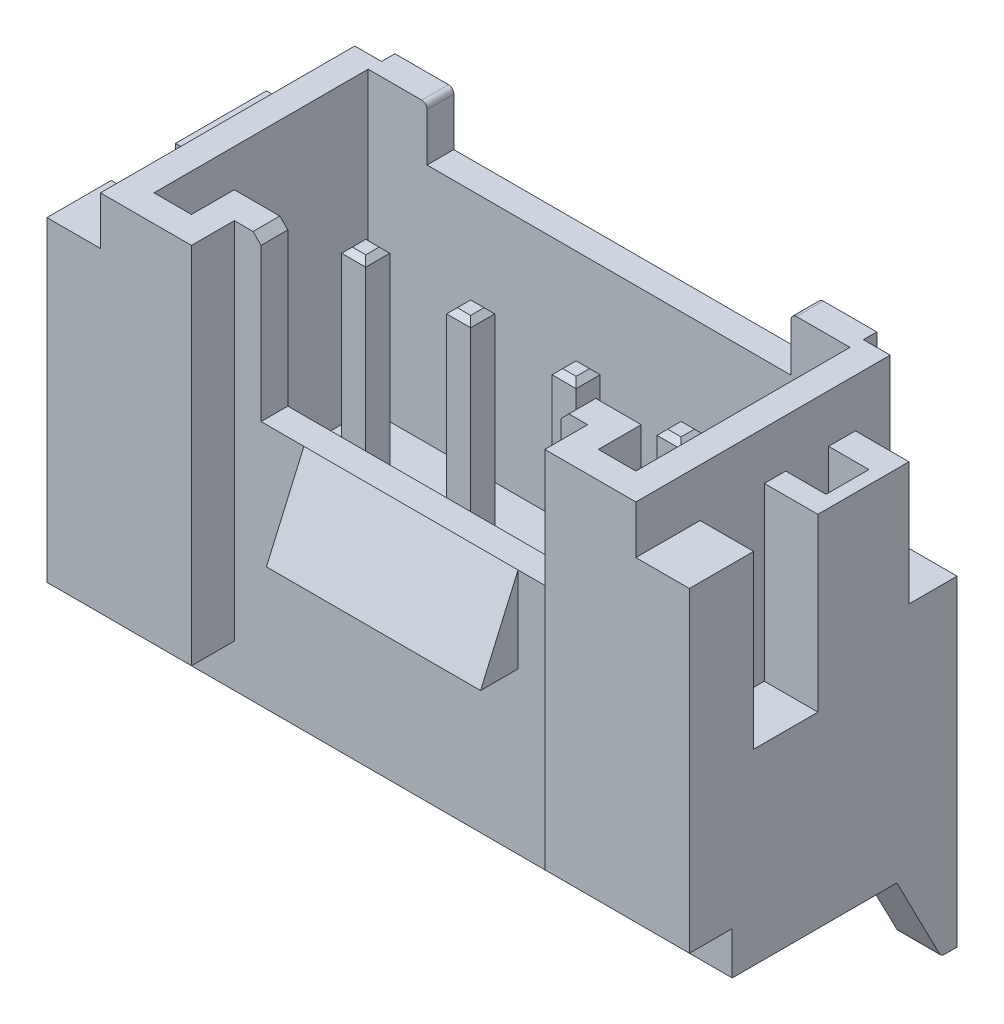
SolidWorks part; units mm, degrees
ref_plane "Plan de face" through (0, 0, 0) normal (0, 0, 1) x (1, 0, 0)
ref_plane "Plan de dessus" through (0, 0, 0) normal (0, 1, 0) x (1, 0, 0)
ref_plane "Plan de droite" through (0, 0, 0) normal (1, 0, 0) x (0, 0, -1)
sketch "Esquisse1" plane through (0, 0, 0) normal (0, 1, 0) x (1, 0, 0)
  line L1 (0, 0) -> (10, 0)
  line L2 (0, 0) -> (0, 5)
  line L3 (0, 5) -> (10, 5)
  line L4 (10, 0) -> (10, 5)
  dimension "D1" = 5
  dimension "D2" = 10
extrude "Boss.-Extru.1" add sketch "Esquisse1" along normal blind 7.6
sketch "Esquisse2" plane through (0, 7.6, 0) normal (0, 1, 0) x (1, 0, 0)
  line L0 (0, 0) -> (10, 0) construction
  line L1 (1.7, 0) -> (8.3, 0)
  line L2 (1.7, 0) -> (1.7, 0.8)
  line L3 (1.7, 0.8) -> (8.3, 0.8)
  line L4 (8.3, 0) -> (8.3, 0.8)
  line L5 (0, 5) -> (0, 0) construction
  line L6 (10, 0) -> (10, 5) construction
  dimension "D1" = 1.7
  dimension "D2" = 1.7
  dimension "D3" = 0.8
extrude "Enlèv. mat.-Extru.1" cut sketch "Esquisse2" against normal blind 8
sketch "Esquisse4" plane through (0, 7.6, 0) normal (0, 1, 0) x (1, 0, 0)
  line L16 (0.5, 0.5) -> (1.2, 0.5)
  line L17 (1.2, 0.5) -> (1.2, 1.3)
  line L18 (1.2, 1.3) -> (8.8, 1.3)
  line L19 (8.8, 1.3) -> (8.8, 0.5)
  line L20 (8.8, 0.5) -> (9.5, 0.5)
  line L21 (9.5, 0.5) -> (9.5, 4.5)
  line L22 (9.5, 4.5) -> (0.5, 4.5)
  line L23 (0.5, 4.5) -> (0.5, 0.5)
  line L24 (0.5, 0.5) -> (1.2, 0.5)
  line L25 (1.2, 0.5) -> (1.2, 1.3)
  line L26 (1.2, 1.3) -> (8.8, 1.3)
  line L27 (8.8, 1.3) -> (8.8, 0.5)
  line L28 (8.8, 0.5) -> (9.5, 0.5)
  line L29 (9.5, 0.5) -> (9.5, 4.5)
  line L30 (9.5, 4.5) -> (0.5, 4.5)
  line L31 (0.5, 4.5) -> (0.5, 0.5)
  dimension "D1" = 0.5
extrude "Enlèv. mat.-Extru.2" cut sketch "Esquisse4" against normal blind 5.5
sketch "Esquisse5" plane through (0, 7.6, 0) normal (0, 1, 0) x (1, 0, 0)
  line L0 (10, 5) -> (0, 5) construction
  line L1 (1.6, 5) -> (8.4, 5)
  line L2 (1.6, 5) -> (1.6, 4.5)
  line L3 (1.6, 4.5) -> (8.4, 4.5)
  line L4 (8.4, 5) -> (8.4, 4.5)
  line L5 (9.5, 4.5) -> (0.5, 4.5) construction
  line L6 (10, 0) -> (10, 5) construction
  line L7 (0, 5) -> (0, 0) construction
  dimension "D1" = 1.6
  dimension "D2" = 1.6
extrude "Enlèv. mat.-Extru.3" cut sketch "Esquisse5" against normal blind 1
sketch "Esquisse6" plane through (0, 7.6, 0) normal (0, 1, 0) x (1, 0, 0)
  line L0 (1.2, 1.3) -> (8.8, 1.3) construction
  line L1 (2.2, 1.3) -> (7.8, 1.3)
  line L2 (2.2, 1.3) -> (2.2, 0.8)
  line L3 (2.2, 0.8) -> (7.8, 0.8)
  line L4 (7.8, 1.3) -> (7.8, 0.8)
  line L5 (8.3, 0.8) -> (1.7, 0.8) construction
  line L6 (10, 0) -> (10, 5) construction
  line L7 (0, 5) -> (0, 0) construction
  dimension "D1" = 2.2
  dimension "D2" = 2.2
extrude "Enlèv. mat.-Extru.4" cut sketch "Esquisse6" against normal blind 3
sketch "Esquisse8" plane through (0, 0, 0) normal (0, -1, 0) x (1, 0, 0)
  line L0 (8.3, -0.8) -> (1.7, -0.8) construction
  line L1 (1.7, -0.8) -> (8.3, -0.8)
  line L2 (1.7, -0.8) -> (1.7, -5)
  line L3 (1.7, -5) -> (8.3, -5)
  line L4 (8.3, -0.8) -> (8.3, -5)
  line L5 (10, -5) -> (0, -5) construction
  line L6 (0, -5) -> (0, 0) construction
  line L7 (10, 0) -> (10, -5) construction
  dimension "D1" = 1.7
  dimension "D2" = 1.7
extrude "Enlèv. mat.-Extru.6" cut sketch "Esquisse8" against normal blind 0.9
sketch "Esquisse9" plane through (1.7, 0, 0) normal (1, 0, 0) x (0, 0, -1)
  line L1 (4.7101, 0.9771) -> (3.4, 0)
  line L2 (3.4, 0) -> (2.4, 0)
  line L3 (2.4, 0) -> (1.0899, 0.9771)
  line L5 (4.7101, 0.9771) -> (1.0899, 0.9771)
  line L6 (5, 0.9) -> (0.8, 0.9) construction
  line L7 (2.9, 0) -> (2.9, 0.9771) construction
  dimension "D2" = 1
  dimension "D4" = 0.3
  dimension "D5" = 0.3
extrude "Boss.-Extru.2" add sketch "Esquisse9" along normal blind 6.8
ref_plane "Plan1" through (5, 0, 0) normal (1, 0, 0) x (0, 0, -1)
sketch "Esquisse11" plane through (5, 0, 0) normal (1, 0, 0) x (0, 0, -1)
  line L0 (0.8, 4.6) -> (0.1, 3)
  line L1 (0.1, 3) -> (0.8, 3)
  line L2 (0.8, 0.9) -> (0.8, 7.6) construction
  line L3 (0.8, 3) -> (0.8, 4.6)
  dimension "D1" = 1.6
  dimension "D2" = 0.7
extrude "Boss.-Extru.3" add sketch "Esquisse11" along normal blind 2 and the other way blind 2
ref_plane "Plan2" through (0, 1, 0) normal (0, 1, 0) x (1, 0, 0)
sketch "Esquisse17" plane through (0, 1, 0) normal (0, 1, 0) x (1, 0, 0)
  line L0 (3.035, 0.8) -> (3.035, 5) construction
  line L1 (5, 0.8) -> (5, 5) construction
  line L2 (6.965, 0.8) -> (6.965, 5) construction
  line L4 (1.7, 0.8) -> (1.7, 5) construction
  line L8 (2.41, 0.8) -> (3.66, 0.8)
  line L9 (3.66, 0.8) -> (3.66, 5)
  line L10 (3.66, 5) -> (2.41, 5)
  line L11 (2.41, 5) -> (2.41, 0.8)
  line L16 (4.375, 0.8) -> (5.625, 0.8)
  line L17 (5.625, 0.8) -> (5.625, 5)
  line L18 (5.625, 5) -> (4.375, 5)
  line L19 (4.375, 5) -> (4.375, 0.8)
  line L24 (6.34, 0.8) -> (7.59, 0.8)
  line L25 (7.59, 0.8) -> (7.59, 5)
  line L26 (7.59, 5) -> (6.34, 5)
  line L27 (6.34, 5) -> (6.34, 0.8)
  dimension "D1" = 1.25
  dimension "D2" = 1.25
  dimension "D3" = 1.25
  dimension "D4" = 3.3
  dimension "D5" = 1.34
  dimension "D6" = 1.34
extrude "Boss.-Extru.8" add sketch "Esquisse17" against normal blind 1
chamfer "Chanfrein1" distance 0.15 angle 45 2 edges at (2.2, 7.6, -1.05) (7.8, 7.6, -1.05)
sketch "Esquisse13" plane through (0, 0, 0) normal (0, -1, 0) x (1, 0, 0)
  line L0 (5, -0.8) -> (5, -5) construction
  line L1 (1.83, -2.675) -> (2.28, -2.675)
  line L2 (1.83, -2.675) -> (1.83, -3.125)
  line L3 (1.83, -3.125) -> (2.28, -3.125)
  line L4 (2.28, -2.675) -> (2.28, -3.125)
  line L5 (4.24, -3.125) -> (3.79, -3.125)
  line L6 (3.79, -2.675) -> (3.79, -3.125)
  line L7 (4.24, -2.675) -> (4.24, -3.125)
  line L8 (4.24, -2.675) -> (3.79, -2.675)
  line L9 (2.055, -2.675) -> (2.055, -3.125) construction
  line L10 (1.7, -2.4) -> (1.7, 0) construction
  line L11 (2.41, -0.8) -> (3.66, -0.8) construction
  line L14 (1.83, -2.9) -> (2.28, -2.9) construction
  line L15 (2.41, -2.4) -> (1.7, -2.4) construction
  line L16 (3.035, -0.8) -> (3.035, -5) construction
  line L19 (5.76, -3.125) -> (6.21, -3.125)
  line L20 (5.76, -2.675) -> (5.76, -3.125)
  line L21 (5.76, -2.675) -> (6.21, -2.675)
  line L22 (6.21, -2.675) -> (6.21, -3.125)
  line L23 (7.72, -2.675) -> (7.72, -3.125)
  line L24 (8.17, -3.125) -> (7.72, -3.125)
  line L25 (8.17, -2.675) -> (8.17, -3.125)
  line L26 (8.17, -2.675) -> (7.72, -2.675)
  point P14 (3.035, -0.8)
  dimension "D1" = 0.355
  dimension "D2" = 0.45
  dimension "D3" = 0.45
  dimension "D4" = 0.5
  dimension "D5" = 0
extrude "Boss.-Extru.5" add sketch "Esquisse13" along normal blind 0.45 and the other way blind 6.3
sketch "Esquisse18" plane through (0, 0.9, 0) normal (0, -1, 0) x (1, 0, 0)
  line L1 (1.7, -0.8) -> (2.41, -0.8)
  line L2 (1.7, -0.8) -> (1.7, -1.1933)
  line L3 (1.7, -1.1933) -> (2.41, -1.1933)
  line L4 (2.41, -0.8) -> (2.41, -1.1933)
  line L5 (3.66, -0.8) -> (4.375, -0.8)
  line L6 (3.66, -0.8) -> (3.66, -1.1933)
  line L7 (3.66, -1.1933) -> (4.375, -1.1933)
  line L8 (4.375, -0.8) -> (4.375, -1.1933)
  line L9 (5.625, -0.8) -> (6.34, -0.8)
  line L10 (5.625, -0.8) -> (5.625, -1.1933)
  line L11 (5.625, -1.1933) -> (6.34, -1.1933)
  line L12 (6.34, -0.8) -> (6.34, -1.1933)
  line L13 (7.59, -0.8) -> (8.3, -0.8)
  line L14 (7.59, -0.8) -> (7.59, -1.1933)
  line L15 (7.59, -1.1933) -> (8.3, -1.1933)
  line L16 (8.3, -0.8) -> (8.3, -1.1933)
extrude "Boss.-Extru.9" add sketch "Esquisse18" along normal blind 0.9
chamfer "Chanfrein2" distance 0.1 angle 45 16 edges at (7.945, 6.3, -2.675) (8.17, 6.3, -2.9) (7.72, 6.3, -2.9) (7.945, 6.3, -3.125) (5.985, 6.3, -2.675) (6.21, 6.3, -2.9) (5.985, 6.3, -3.125) (5.76, 6.3, -2.9) (4.015, 6.3, -2.675) (4.24, 6.3, -2.9) (4.015, 6.3, -3.125) (3.79, 6.3, -2.9) (1.83, 6.3, -2.9) (2.055, 6.3, -3.125) (2.28, 6.3, -2.9) (2.055, 6.3, -2.675)
sketch "Esquisse14" plane through (0, 0, -3.125) normal (0, 0, -1) x (-1, 0, 0)
  line L0 (-7.72, 0) -> (-7.72, -0.45) construction
  line L1 (-8.17, -0.45) -> (-7.72, -0.45)
  line L2 (-8.17, -0.45) -> (-8.17, -0.02)
  line L3 (-8.17, -0.02) -> (-7.72, -0.02)
  line L4 (-7.72, -0.45) -> (-7.72, -0.02)
  line L5 (-6.965, 0) -> (-6.965, 1.119) construction
  line L6 (-7.59, 0) -> (-6.34, 0) construction
  line L7 (-5, 0) -> (-5, 1.119) construction
  line L9 (-5.76, -0.45) -> (-6.21, -0.45)
  line L10 (-6.21, -0.45) -> (-6.21, -0.02)
  line L11 (-5.76, -0.45) -> (-5.76, -0.02)
  line L12 (-5.76, -0.02) -> (-6.21, -0.02)
  line L13 (-4.24, -0.45) -> (-3.79, -0.45)
  line L14 (-4.24, -0.45) -> (-4.24, -0.02)
  line L15 (-4.24, -0.02) -> (-3.79, -0.02)
  line L16 (-3.79, -0.45) -> (-3.79, -0.02)
  line L17 (-1.83, -0.45) -> (-2.28, -0.45)
  line L18 (-2.28, -0.45) -> (-2.28, -0.02)
  line L19 (-1.83, -0.45) -> (-1.83, -0.02)
  line L20 (-1.83, -0.02) -> (-2.28, -0.02)
  point P9 (-6.965, 0)
  dimension "D1" = 0.43
  dimension "D2" = 0
extrude "Boss.-Extru.6" add sketch "Esquisse14" along normal blind 1.875
fillet "Congé1" radius 0.1 8 edges at (2.055, -0.02, -3.125) (4.015, -0.02, -3.125) (5.985, -0.02, -3.125) (7.945, -0.02, -3.125) (2.055, -0.45, -2.675) (4.015, -0.45, -2.675) (5.985, -0.45, -2.675) (7.945, -0.45, -2.675)
fillet "Congé2" radius 0.1 2 edges at (8.4, 7.6, -4.75) (1.6, 7.6, -4.75)
ref_plane "Plan3" through (0, 6.7, 0) normal (0, 1, 0) x (1, 0, 0)
sketch "Esquisse21" plane through (0, 6.7, 0) normal (0, 1, 0) x (1, 0, 0)
  line L1 (0, 5) -> (-1, 5)
  line L2 (0, 5) -> (0, 0)
  line L3 (0, 0) -> (-1, 0)
  line L4 (-1, 5) -> (-1, 0)
  line L5 (10, 5) -> (11, 5)
  line L6 (10, 5) -> (10, 0)
  line L7 (10, 0) -> (11, 0)
  line L8 (11, 5) -> (11, 0)
  dimension "D1" = 1
  dimension "D2" = 1
extrude "Boss.-Extru.10" add sketch "Esquisse21" against normal blind 6.7
sketch "Esquisse22" plane through (11, 0, 0) normal (1, 0, 0) x (0, 0, -1)
  line L1 (0, 0) -> (0.8, 0)
  line L2 (0, 0) -> (0, 0.8)
  line L3 (0, 0.8) -> (0.8, 0.8)
  line L4 (0.8, 0) -> (0.8, 0.8)
  dimension "D1" = 0.8
  dimension "D2" = 0.8
extrude "Enlèv. mat.-Extru.8" cut sketch "Esquisse22" against normal blind 12
sketch "Esquisse23" plane through (0, 6.7, 0) normal (0, 1, 0) x (1, 0, 0)
  line L0 (5, 5) -> (5, 0.1) construction
  line L1 (10, 5) -> (10, 0) construction
  line L2 (11, 5) -> (10, 5)
  line L3 (11, 5) -> (11, 4.1)
  line L4 (11, 4.1) -> (10, 4.1)
  line L5 (10, 4.75) -> (10, 4.1)
  line L6 (8.4, 5) -> (1.6, 5) construction
  line L7 (10.7525, 3.6) -> (10, 3.6)
  line L8 (10.7525, 3.6) -> (10.7525, 2.8)
  line L9 (10.7525, 2.8) -> (10, 2.8)
  line L10 (10, 3.6) -> (10, 2.8)
  line L11 (10, 5) -> (9.5, 5)
  line L12 (-0.7525, 2.8) -> (0, 2.8)
  line L13 (10, 4.75) -> (9.5, 4.75)
  line L14 (9.5, 5) -> (9.5, 4.75)
  line L15 (3, 0.1) -> (7, 0.1) construction
  line L16 (-0.7525, 3.6) -> (-0.7525, 2.8)
  line L17 (0, 3.6) -> (0, 2.8)
  line L18 (-0.7525, 3.6) -> (0, 3.6)
  line L19 (0, 4.75) -> (0, 4.1)
  line L20 (-1, 4.1) -> (0, 4.1)
  line L21 (-1, 5) -> (-1, 4.1)
  line L22 (-1, 5) -> (0, 5)
  line L23 (0, 5) -> (0.5, 5)
  line L24 (0.5, 5) -> (0.5, 4.75)
  line L25 (0, 4.75) -> (0.5, 4.75)
  dimension "D1" = 0.5
  dimension "D2" = 0.25
  dimension "D3" = 0.9
  dimension "D4" = 2.2
  dimension "D5" = 1.4
extrude "Enlèv. mat.-Extru.9" cut sketch "Esquisse23" against normal blind 2.3 and the other way blind 0.9
sketch "Esquisse24" plane through (0, 6.7, 0) normal (0, 1, 0) x (1, 0, 0)
  line L0 (10, 2.8) -> (10, 0) construction
  line L1 (10, 1.2) -> (11, 1.2)
  line L2 (10, 1.2) -> (10, 2.4)
  line L3 (10, 2.4) -> (11, 2.4)
  line L4 (11, 1.2) -> (11, 2.4)
  line L5 (11, 0) -> (11, 4.1) construction
  line L6 (10, 0) -> (11, 0) construction
  line L7 (5, 5) -> (5, 0.1) construction
  line L8 (8.4, 5) -> (1.6, 5) construction
  line L9 (3, 0.1) -> (7, 0.1) construction
  line L10 (0, 1.2) -> (0, 2.4)
  line L11 (0, 1.2) -> (-1, 1.2)
  line L12 (-1, 1.2) -> (-1, 2.4)
  line L13 (0, 2.4) -> (-1, 2.4)
  dimension "D1" = 1.2
  dimension "D2" = 1.2
extrude "Enlèv. mat.-Extru.10" cut sketch "Esquisse24" against normal blind 3.2
sketch "Esquisse25" plane through (0, -0.45, 0) normal (0, -1, 0) x (1, 0, 0)
  line L0 (2.28, -5) -> (2.28, -2.775) construction
  line L1 (1.83, -5) -> (2.28, -5)
  line L2 (1.83, -5) -> (1.83, -4.55)
  line L3 (1.83, -4.55) -> (2.28, -4.55)
  line L4 (2.28, -5) -> (2.28, -4.55)
  line L5 (3.66, -3.4) -> (2.41, -3.4) construction
  line L6 (4.375, -3.4) -> (5.625, -3.4) construction
  line L7 (2.41, -5) -> (3.66, -5) construction
  line L8 (4.375, -5) -> (5.625, -5)
  line L9 (3.035, -3.4) -> (3.035, -5) construction
  line L10 (4.24, -5) -> (3.79, -5)
  line L11 (5, -3.4) -> (5, -5) construction
  line L12 (3.79, -5) -> (3.79, -4.55)
  line L13 (4.24, -5) -> (4.24, -4.55)
  line L14 (4.24, -4.55) -> (3.79, -4.55)
  line L15 (5.76, -5) -> (6.21, -5)
  line L16 (5.76, -5) -> (5.76, -4.55)
  line L17 (5.76, -4.55) -> (6.21, -4.55)
  line L18 (6.21, -5) -> (6.21, -4.55)
  line L19 (8.17, -5) -> (7.72, -5)
  line L20 (7.72, -5) -> (7.72, -4.55)
  line L21 (8.17, -5) -> (8.17, -4.55)
  line L22 (8.17, -4.55) -> (7.72, -4.55)
  line M1 (2.28, -5) -> (2.28, -2.775)
  line M3 (1.83, -2.775) -> (1.83, -5)
  line M4 (1.83, -5) -> (2.28, -5)
  dimension "D1" = 0.45
extrude "Boss.-Extru.11" add sketch "Esquisse25" along normal blind 1.9 contours L3 M3 M4 M1 | L13 L14 L12 L10 | L15 L18 L17 L16 | L21 L22 L20 L19 region at (2.055, -0.45, -4.775) region at (4.015, -0.45, -4.775) region at (5.985, -0.45, -4.775) region at (7.945, -0.45, -4.775)
fillet "Congé3" radius 0.1 8 edges at (4.015, -0.02, -5) (5.985, -0.02, -5) (7.945, -0.02, -5) (2.055, -0.02, -5) (7.945, -0.45, -4.55) (5.985, -0.45, -4.55) (4.015, -0.45, -4.55) (2.055, -0.45, -4.55)
fillet "Congé4" radius 0.2 4 edges at (7.945, -2.35, -4.55) (5.985, -2.35, -4.55) (4.015, -2.35, -4.55) (2.055, -2.35, -4.55)
sketch "Esquisse27" plane through (-1, 0, 0) normal (-1, 0, 0) x (0, 0, 1)
  line L0 (-5, 0) -> (-5, -2.5474) construction
  line L1 (-5, -2.5474) -> (500000, -0.784) construction
  line L2 (-5, 0) -> (-5, -1.6)
  line L3 (-5, -1.6) -> (-4.761, -1.6)
  line L4 (-4.6721, -1.5458) -> (-3.8754, 0)
  line L5 (-5, 0) -> (-0.8, 0) construction
  line L6 (-3.8754, 0) -> (-5, 0)
  arc A0 (-4.761, -1.6) -> (-4.6721, -1.5458) centre (-4.761, -1.5) ccw
  point P11 (-4.7, -1.6)
  dimension "D4" = 0.1
  dimension "D1" = 1.6
  dimension "D2" = 0.3
  dimension "D3" = 1.8
extrude "Boss.-Extru.12" add sketch "Esquisse27" against normal blind 0.8
sketch "Esquisse28" plane through (11, 0, 0) normal (1, 0, 0) x (0, 0, -1)
  line L4 (5, -1.6) -> (5, 0)
  line L5 (4.761, -1.6) -> (5, -1.6)
  line L6 (3.8754, 0) -> (4.6721, -1.5458)
  line L7 (5, 0) -> (3.8754, 0)
  line L8 (5, -1.6) -> (5, 0)
  line L9 (4.761, -1.6) -> (5, -1.6)
  line L10 (3.8754, 0) -> (4.6721, -1.5458)
  line L11 (5, 0) -> (3.8754, 0)
  arc A1 (4.6721, -1.5458) -> (4.761, -1.6) centre (4.761, -1.5) ccw
  arc A2 (4.6721, -1.5458) -> (4.761, -1.6) centre (4.761, -1.5) ccw
  dimension "D1" = 0
extrude "Boss.-Extru.13" add sketch "Esquisse28" against normal blind 0.8
